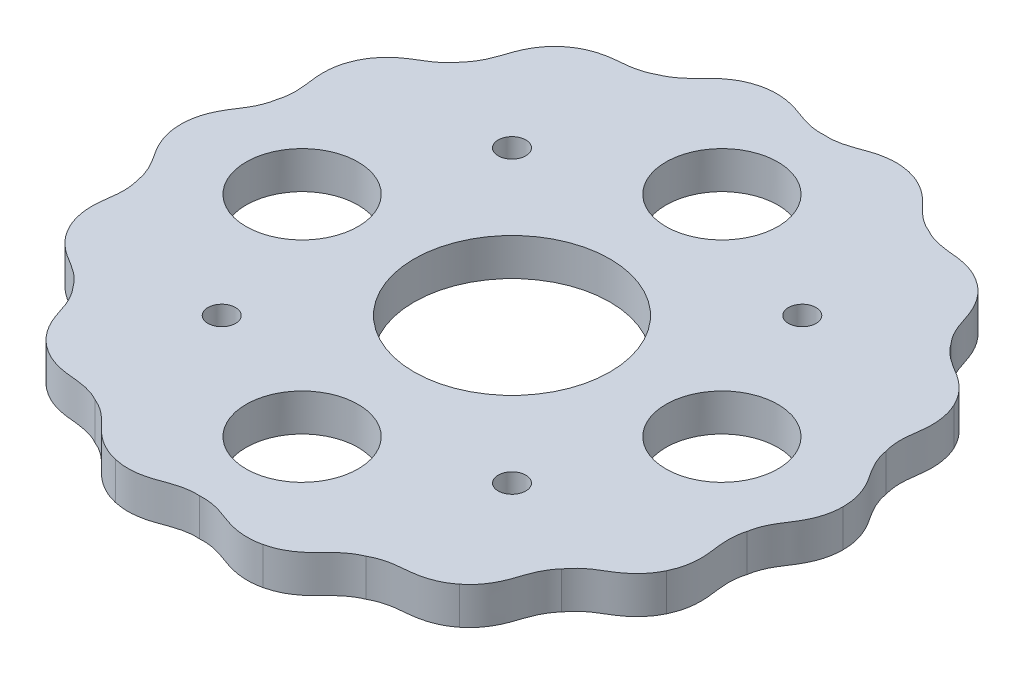
SolidWorks part; units mm, degrees
ref_plane "Front Plane" through (0, 0, 0) normal (0, 0, 1) x (1, 0, 0)
ref_plane "Top Plane" through (0, 0, 0) normal (0, 1, 0) x (1, 0, 0)
ref_plane "Right Plane" through (0, 0, 0) normal (1, 0, 0) x (0, 0, -1)
sketch "Sketch1" plane through (0, 0, 0) normal (0, 1, 0) x (1, 0, 0)
  line L0 (0, 0) -> (37.5, 0) construction
  line L1 (0, 0) -> (37.4807, 1.2019) construction
  line L2 (0, 0) -> (37.423, 2.4026) construction
  line L3 (0, 0) -> (37.3267, 3.6009) construction
  line L4 (0, 0) -> (37.1921, 4.7954) construction
  line L5 (0, 0) -> (37.0193, 5.985) construction
  line L6 (0, 0) -> (36.8085, 7.1684) construction
  line L7 (0, 0) -> (36.5598, 8.3445) construction
  line L8 (0, 0) -> (36.2736, 9.512) construction
  line L9 (0, 0) -> (35.95, 10.6698) construction
  line L10 (0, 0) -> (35.5896, 11.8166) construction
  line L11 (0, 0) -> (35.1926, 12.9512) construction
  line L12 (0, 0) -> (34.7594, 14.0725) construction
  line L13 (0, 0) -> (34.2905, 15.1794) construction
  line L14 (0, 0) -> (33.7863, 16.2706) construction
  line L15 (37.5, 0) -> (38.5, 0) construction
  line L16 (37.4807, 1.2019) -> (38.3521, 1.6927) construction
  line L17 (37.423, 2.4026) -> (37.9413, 3.2578) construction
  line L18 (37.3267, 3.6009) -> (37.3588, 4.6003) construction
  line L19 (37.1921, 4.7954) -> (36.7296, 5.682) construction
  line L20 (37.0193, 5.985) -> (36.1812, 6.5305) construction
  line L21 (36.8085, 7.1684) -> (35.8105, 7.2325) construction
  line L22 (36.5598, 8.3445) -> (35.5849, 8.122) construction
  line L23 (37, 0.0019) -> (37, 0)
  line L24 (33.3367, 16.052) -> (33.3358, 16.0537)
  line L25 (37, -0.0019) -> (37, 0)
  line L26 (33.3367, -16.052) -> (33.3358, -16.0537)
  line L27 (33.335, -16.0554) -> (33.3358, -16.0537)
  line L28 (23.0706, -28.9266) -> (23.0691, -28.9278)
  line L29 (23.0677, -28.9289) -> (23.0691, -28.9278)
  line L30 (8.2351, -36.0719) -> (8.2333, -36.0723)
  line L31 (8.2315, -36.0727) -> (8.2333, -36.0723)
  line L32 (-8.2315, -36.0727) -> (-8.2333, -36.0723)
  line L33 (-8.2351, -36.0719) -> (-8.2333, -36.0723)
  line L34 (-23.0677, -28.9289) -> (-23.0691, -28.9278)
  line L35 (-23.0706, -28.9266) -> (-23.0691, -28.9278)
  line L36 (-33.335, -16.0554) -> (-33.3358, -16.0537)
  line L37 (-33.3367, -16.052) -> (-33.3358, -16.0537)
  line L38 (-37, -0.0019) -> (-37, 0)
  line L39 (-37, 0.0019) -> (-37, 0)
  line L40 (-33.3367, 16.052) -> (-33.3358, 16.0537)
  line L41 (-33.335, 16.0554) -> (-33.3358, 16.0537)
  line L42 (-23.0706, 28.9266) -> (-23.0691, 28.9278)
  line L43 (-23.0677, 28.9289) -> (-23.0691, 28.9278)
  line L44 (-8.2351, 36.0719) -> (-8.2333, 36.0723)
  line L45 (-8.2315, 36.0727) -> (-8.2333, 36.0723)
  line L46 (8.2315, 36.0727) -> (8.2333, 36.0723)
  line L47 (8.2351, 36.0719) -> (8.2333, 36.0723)
  line L48 (23.0677, 28.9289) -> (23.0691, 28.9278)
  line L49 (23.0706, 28.9266) -> (23.0691, 28.9278)
  line L50 (33.335, 16.0554) -> (33.3358, 16.0537)
  line L51 (35.5, 0.0037) -> (35.5, 0)
  line L52 (31.986, 15.3995) -> (31.9844, 15.4029)
  line L53 (35.5, -0.0037) -> (35.5, 0)
  line L54 (31.986, -15.3995) -> (31.9844, -15.4029)
  line L55 (31.9828, -15.4062) -> (31.9844, -15.4029)
  line L56 (22.1368, -27.7527) -> (22.1339, -27.755)
  line L57 (22.131, -27.7573) -> (22.1339, -27.755)
  line L58 (7.9031, -34.6091) -> (7.8995, -34.6099)
  line L59 (7.8959, -34.6108) -> (7.8995, -34.6099)
  line L60 (-7.8959, -34.6108) -> (-7.8995, -34.6099)
  line L61 (-7.9031, -34.6091) -> (-7.8995, -34.6099)
  line L62 (-22.131, -27.7573) -> (-22.1339, -27.755)
  line L63 (-22.1368, -27.7527) -> (-22.1339, -27.755)
  line L64 (-31.9828, -15.4062) -> (-31.9844, -15.4029)
  line L65 (-31.986, -15.3995) -> (-31.9844, -15.4029)
  line L66 (-35.5, -0.0037) -> (-35.5, 0)
  line L67 (-35.5, 0.0037) -> (-35.5, 0)
  line L68 (-31.986, 15.3995) -> (-31.9844, 15.4029)
  line L69 (-31.9828, 15.4062) -> (-31.9844, 15.4029)
  line L70 (-22.1368, 27.7527) -> (-22.1339, 27.755)
  line L71 (-22.131, 27.7573) -> (-22.1339, 27.755)
  line L72 (-7.9031, 34.6091) -> (-7.8995, 34.6099)
  line L73 (-7.8959, 34.6108) -> (-7.8995, 34.6099)
  line L74 (7.8959, 34.6108) -> (7.8995, 34.6099)
  line L75 (7.9031, 34.6091) -> (7.8995, 34.6099)
  line L76 (22.131, 27.7573) -> (22.1339, 27.755)
  line L77 (22.1368, 27.7527) -> (22.1339, 27.755)
  line L78 (31.9828, 15.4062) -> (31.9844, 15.4029)
  circle A0 centre (0, 0) radius 35 construction
  circle A1 centre (37.5, 0) radius 2.5 construction
  circle A2 centre (0, 0) radius 37.5 construction
  spline S0 degree 3 poles (35.5849, 8.122) (35.6266, 7.5364) (36.0345, 6.7125) (36.7836, 5.6218) (37.4152, 4.5501) (38.2239, 2.702) (38.5014, 1.1074) (38.5, 0) knots 0 0 0 0 0.195516 0.310928 0.453873 0.621058 1 1 1 1
  spline S1 degree 3 poles (35.5849, 8.122) (35.3683, 8.6678) (35.3784, 9.5871) (35.5801, 10.8948) (35.6841, 12.1344) (35.611, 14.1503) (35.169, 15.7074) (34.6873, 16.7045) knots 0 0 0 0 0.195516 0.310928 0.453873 0.621058 1 1 1 1
  spline S2 degree 1 poles (34.1119, 7.7858) (33.3367, 16.052) knots 0 0 1 1 construction
  spline S3 degree 1 poles (34.1119, 7.7858) (37, 0.0019) knots 0 0 1 1 construction
  spline S4 degree 3 poles (33.3367, 16.052) (33.6005, 15.5058) (33.9037, 14.6401) (34.1146, 13.4372) (34.174, 12.5211) (34.1413, 11.5771) (34.0239, 10.6392) (33.8823, 9.6155) (33.9055, 8.625) (34.0243, 8.0514) (34.1119, 7.7858) knots 0.015853 0.015853 0.015853 0.015853 0.26189 0.384908 0.507927 0.630945 0.753963 0.876982 0.938491 1 1 1 1
  spline S5 degree 3 poles (34.1119, 7.7858) (34.1483, 7.5085) (34.2901, 6.9402) (34.6989, 6.0377) (35.2706, 5.1769) (35.7834, 4.3828) (36.2224, 3.5464) (36.5664, 2.6953) (36.8983, 1.52) (37.0008, 0.6085) (37, 0.0019) knots 0.015853 0.015853 0.015853 0.015853 0.077362 0.138872 0.26189 0.384908 0.507927 0.630945 0.753963 1 1 1 1
  spline S6 degree 3 poles (37, -0.0019) (37.0008, -0.6085) (36.8983, -1.52) (36.5664, -2.6953) (36.2224, -3.5464) (35.7834, -4.3828) (35.2706, -5.1769) (34.6989, -6.0377) (34.2901, -6.9402) (34.1483, -7.5085) (34.1119, -7.7858) knots 0.015853 0.015853 0.015853 0.015853 0.26189 0.384908 0.507927 0.630945 0.753963 0.876982 0.938491 1 1 1 1
  spline S7 degree 3 poles (34.1119, -7.7858) (34.0243, -8.0514) (33.9055, -8.625) (33.8823, -9.6155) (34.0239, -10.6392) (34.1413, -11.5771) (34.174, -12.5211) (34.1146, -13.4372) (33.9037, -14.6401) (33.6005, -15.5058) (33.3367, -16.052) knots 0.015853 0.015853 0.015853 0.015853 0.077362 0.138872 0.26189 0.384908 0.507927 0.630945 0.753963 1 1 1 1
  spline S8 degree 3 poles (33.335, -16.0554) (33.0725, -16.6022) (32.5847, -17.3791) (31.7758, -18.2939) (31.0965, -18.9115) (30.3381, -19.4746) (29.5316, -19.9675) (28.6429, -20.4951) (27.8831, -21.1308) (27.5087, -21.5813) (27.3556, -21.8154) knots 0.015853 0.015853 0.015853 0.015853 0.26189 0.384908 0.507927 0.630945 0.753963 0.876982 0.938491 1 1 1 1
  spline S9 degree 3 poles (27.3556, -21.8154) (27.1615, -22.0167) (26.8056, -22.4819) (26.3549, -23.3642) (26.0383, -24.348) (25.7371, -25.2439) (25.357, -26.1087) (24.906, -26.9083) (24.1941, -27.9005) (23.5453, -28.549) (23.0706, -28.9266) knots 0.015853 0.015853 0.015853 0.015853 0.077362 0.138872 0.26189 0.384908 0.507927 0.630945 0.753963 1 1 1 1
  spline S10 degree 3 poles (23.0677, -28.9289) (22.5939, -29.3077) (21.8173, -29.796) (20.6915, -30.2693) (19.8116, -30.531) (18.884, -30.7092) (17.9435, -30.8034) (16.9139, -30.8931) (15.9535, -31.1362) (15.4207, -31.3797) (15.1812, -31.5241) knots 0.015853 0.015853 0.015853 0.015853 0.26189 0.384908 0.507927 0.630945 0.753963 0.876982 0.938491 1 1 1 1
  spline S11 degree 3 poles (15.1812, -31.5241) (14.919, -31.6213) (14.3964, -31.886) (13.6076, -32.4854) (12.8955, -33.2344) (12.2354, -33.9109) (11.5177, -34.5251) (10.7645, -35.0499) (9.6926, -35.6349) (8.8266, -35.9377) (8.2351, -36.0719) knots 0.015853 0.015853 0.015853 0.015853 0.077362 0.138872 0.26189 0.384908 0.507927 0.630945 0.753963 1 1 1 1
  spline S12 degree 3 poles (8.2315, -36.0727) (7.6402, -36.2085) (6.7287, -36.3114) (5.5091, -36.2494) (4.6028, -36.1034) (3.6897, -35.8614) (2.8014, -35.5383) (1.8349, -35.1724) (0.8641, -34.9747) (0.2785, -34.9629) (0, -34.9891) knots 0.015853 0.015853 0.015853 0.015853 0.26189 0.384908 0.507927 0.630945 0.753963 0.876982 0.938491 1 1 1 1
  spline S13 degree 3 poles (0, -34.9891) (-0.2785, -34.9629) (-0.8641, -34.9747) (-1.8349, -35.1724) (-2.8014, -35.5383) (-3.6897, -35.8614) (-4.6028, -36.1034) (-5.5091, -36.2494) (-6.7287, -36.3114) (-7.6402, -36.2085) (-8.2315, -36.0727) knots 0.015853 0.015853 0.015853 0.015853 0.077362 0.138872 0.26189 0.384908 0.507927 0.630945 0.753963 1 1 1 1
  spline S14 degree 3 poles (-8.2351, -36.0719) (-8.8266, -35.9377) (-9.6926, -35.6349) (-10.7645, -35.0499) (-11.5177, -34.5251) (-12.2354, -33.9109) (-12.8955, -33.2344) (-13.6076, -32.4854) (-14.3964, -31.886) (-14.919, -31.6213) (-15.1812, -31.5241) knots 0.015853 0.015853 0.015853 0.015853 0.26189 0.384908 0.507927 0.630945 0.753963 0.876982 0.938491 1 1 1 1
  spline S15 degree 3 poles (-15.1812, -31.5241) (-15.4207, -31.3797) (-15.9535, -31.1362) (-16.9139, -30.8931) (-17.9435, -30.8034) (-18.884, -30.7092) (-19.8116, -30.531) (-20.6915, -30.2693) (-21.8173, -29.796) (-22.5939, -29.3077) (-23.0677, -28.9289) knots 0.015853 0.015853 0.015853 0.015853 0.077362 0.138872 0.26189 0.384908 0.507927 0.630945 0.753963 1 1 1 1
  spline S16 degree 3 poles (-23.0706, -28.9266) (-23.5453, -28.549) (-24.1941, -27.9005) (-24.906, -26.9083) (-25.357, -26.1087) (-25.7371, -25.2439) (-26.0383, -24.348) (-26.3549, -23.3642) (-26.8056, -22.4819) (-27.1615, -22.0167) (-27.3556, -21.8154) knots 0.015853 0.015853 0.015853 0.015853 0.26189 0.384908 0.507927 0.630945 0.753963 0.876982 0.938491 1 1 1 1
  spline S17 degree 3 poles (-27.3556, -21.8154) (-27.5087, -21.5813) (-27.8831, -21.1308) (-28.6429, -20.4951) (-29.5316, -19.9675) (-30.3381, -19.4746) (-31.0965, -18.9115) (-31.7758, -18.2939) (-32.5847, -17.3791) (-33.0725, -16.6022) (-33.335, -16.0554) knots 0.015853 0.015853 0.015853 0.015853 0.077362 0.138872 0.26189 0.384908 0.507927 0.630945 0.753963 1 1 1 1
  spline S18 degree 3 poles (-33.3367, -16.052) (-33.6005, -15.5058) (-33.9037, -14.6401) (-34.1146, -13.4372) (-34.174, -12.5211) (-34.1413, -11.5771) (-34.0239, -10.6392) (-33.8823, -9.6155) (-33.9055, -8.625) (-34.0243, -8.0514) (-34.1119, -7.7858) knots 0.015853 0.015853 0.015853 0.015853 0.26189 0.384908 0.507927 0.630945 0.753963 0.876982 0.938491 1 1 1 1
  spline S19 degree 3 poles (-34.1119, -7.7858) (-34.1483, -7.5085) (-34.2901, -6.9402) (-34.6989, -6.0377) (-35.2706, -5.1769) (-35.7834, -4.3828) (-36.2224, -3.5464) (-36.5664, -2.6953) (-36.8983, -1.52) (-37.0008, -0.6085) (-37, -0.0019) knots 0.015853 0.015853 0.015853 0.015853 0.077362 0.138872 0.26189 0.384908 0.507927 0.630945 0.753963 1 1 1 1
  spline S20 degree 3 poles (-37, 0.0019) (-37.0008, 0.6085) (-36.8983, 1.52) (-36.5664, 2.6953) (-36.2224, 3.5464) (-35.7834, 4.3828) (-35.2706, 5.1769) (-34.6989, 6.0377) (-34.2901, 6.9402) (-34.1483, 7.5085) (-34.1119, 7.7858) knots 0.015853 0.015853 0.015853 0.015853 0.26189 0.384908 0.507927 0.630945 0.753963 0.876982 0.938491 1 1 1 1
  spline S21 degree 3 poles (-34.1119, 7.7858) (-34.0243, 8.0514) (-33.9055, 8.625) (-33.8823, 9.6155) (-34.0239, 10.6392) (-34.1413, 11.5771) (-34.174, 12.5211) (-34.1146, 13.4372) (-33.9037, 14.6401) (-33.6005, 15.5058) (-33.3367, 16.052) knots 0.015853 0.015853 0.015853 0.015853 0.077362 0.138872 0.26189 0.384908 0.507927 0.630945 0.753963 1 1 1 1
  spline S22 degree 3 poles (-33.335, 16.0554) (-33.0725, 16.6022) (-32.5847, 17.3791) (-31.7758, 18.2939) (-31.0965, 18.9115) (-30.3381, 19.4746) (-29.5316, 19.9675) (-28.6429, 20.4951) (-27.8831, 21.1308) (-27.5087, 21.5813) (-27.3556, 21.8154) knots 0.015853 0.015853 0.015853 0.015853 0.26189 0.384908 0.507927 0.630945 0.753963 0.876982 0.938491 1 1 1 1
  spline S23 degree 3 poles (-27.3556, 21.8154) (-27.1615, 22.0167) (-26.8056, 22.4819) (-26.3549, 23.3642) (-26.0383, 24.348) (-25.7371, 25.2439) (-25.357, 26.1087) (-24.906, 26.9083) (-24.1941, 27.9005) (-23.5453, 28.549) (-23.0706, 28.9266) knots 0.015853 0.015853 0.015853 0.015853 0.077362 0.138872 0.26189 0.384908 0.507927 0.630945 0.753963 1 1 1 1
  spline S24 degree 3 poles (-23.0677, 28.9289) (-22.5939, 29.3077) (-21.8173, 29.796) (-20.6915, 30.2693) (-19.8116, 30.531) (-18.884, 30.7092) (-17.9435, 30.8034) (-16.9139, 30.8931) (-15.9535, 31.1362) (-15.4207, 31.3797) (-15.1812, 31.5241) knots 0.015853 0.015853 0.015853 0.015853 0.26189 0.384908 0.507927 0.630945 0.753963 0.876982 0.938491 1 1 1 1
  spline S25 degree 3 poles (-15.1812, 31.5241) (-14.919, 31.6213) (-14.3964, 31.886) (-13.6076, 32.4854) (-12.8955, 33.2344) (-12.2354, 33.9109) (-11.5177, 34.5251) (-10.7645, 35.0499) (-9.6926, 35.6349) (-8.8266, 35.9377) (-8.2351, 36.0719) knots 0.015853 0.015853 0.015853 0.015853 0.077362 0.138872 0.26189 0.384908 0.507927 0.630945 0.753963 1 1 1 1
  spline S26 degree 3 poles (-8.2315, 36.0727) (-7.6402, 36.2085) (-6.7287, 36.3114) (-5.5091, 36.2494) (-4.6028, 36.1034) (-3.6897, 35.8614) (-2.8014, 35.5383) (-1.8349, 35.1724) (-0.8641, 34.9747) (-0.2785, 34.9629) (0, 34.9891) knots 0.015853 0.015853 0.015853 0.015853 0.26189 0.384908 0.507927 0.630945 0.753963 0.876982 0.938491 1 1 1 1
  spline S27 degree 3 poles (0, 34.9891) (0.2785, 34.9629) (0.8641, 34.9747) (1.8349, 35.1724) (2.8014, 35.5383) (3.6897, 35.8614) (4.6028, 36.1034) (5.5091, 36.2494) (6.7287, 36.3114) (7.6402, 36.2085) (8.2315, 36.0727) knots 0.015853 0.015853 0.015853 0.015853 0.077362 0.138872 0.26189 0.384908 0.507927 0.630945 0.753963 1 1 1 1
  spline S28 degree 3 poles (8.2351, 36.0719) (8.8266, 35.9377) (9.6926, 35.6349) (10.7645, 35.0499) (11.5177, 34.5251) (12.2354, 33.9109) (12.8955, 33.2344) (13.6076, 32.4854) (14.3964, 31.886) (14.919, 31.6213) (15.1812, 31.5241) knots 0.015853 0.015853 0.015853 0.015853 0.26189 0.384908 0.507927 0.630945 0.753963 0.876982 0.938491 1 1 1 1
  spline S29 degree 3 poles (15.1812, 31.5241) (15.4207, 31.3797) (15.9535, 31.1362) (16.9139, 30.8931) (17.9435, 30.8034) (18.884, 30.7092) (19.8116, 30.531) (20.6915, 30.2693) (21.8173, 29.796) (22.5939, 29.3077) (23.0677, 28.9289) knots 0.015853 0.015853 0.015853 0.015853 0.077362 0.138872 0.26189 0.384908 0.507927 0.630945 0.753963 1 1 1 1
  spline S30 degree 3 poles (23.0706, 28.9266) (23.5453, 28.549) (24.1941, 27.9005) (24.906, 26.9083) (25.357, 26.1087) (25.7371, 25.2439) (26.0383, 24.348) (26.3549, 23.3642) (26.8056, 22.4819) (27.1615, 22.0167) (27.3556, 21.8154) knots 0.015853 0.015853 0.015853 0.015853 0.26189 0.384908 0.507927 0.630945 0.753963 0.876982 0.938491 1 1 1 1
  spline S31 degree 3 poles (27.3556, 21.8154) (27.5087, 21.5813) (27.8831, 21.1308) (28.6429, 20.4951) (29.5316, 19.9675) (30.3381, 19.4746) (31.0965, 18.9115) (31.7758, 18.2939) (32.5847, 17.3791) (33.0725, 16.6022) (33.335, 16.0554) knots 0.015853 0.015853 0.015853 0.015853 0.077362 0.138872 0.26189 0.384908 0.507927 0.630945 0.753963 1 1 1 1
  spline S32 degree 1 poles (32.6448, 7.451) (35.5, 0.0037) knots 0 0 1 1 construction
  spline S33 degree 1 poles (32.6448, 7.451) (31.986, 15.3995) knots 0 0 1 1 construction
  spline S34 degree 3 poles (35.5, 0.0037) (35.5006, 0.4959) (35.4183, 1.2336) (35.1496, 2.1927) (34.8707, 2.8896) (34.4997, 3.6015) (34.1394, 4.1652) (33.6939, 4.8394) (33.3068, 5.4873) (32.9751, 6.1975) (32.758, 6.8733) (32.6748, 7.2607) (32.6448, 7.451) knots 0.023011 0.023011 0.023011 0.023011 0.267258 0.389382 0.511505 0.633629 0.755753 0.816814 0.877876 0.938938 0.969469 1 1 1 1
  spline S35 degree 3 poles (32.6448, 7.451) (32.5893, 7.6354) (32.4961, 8.0206) (32.3985, 8.7236) (32.3893, 9.5074) (32.4569, 10.2591) (32.5657, 11.0598) (32.6458, 11.724) (32.6712, 12.5264) (32.6201, 13.2752) (32.446, 14.256) (32.2001, 14.9563) (31.986, 15.3995) knots 0.023011 0.023011 0.023011 0.023011 0.053542 0.084072 0.145134 0.206196 0.267258 0.389382 0.511505 0.633629 0.755753 1 1 1 1
  spline S36 degree 3 poles (32.6448, -7.451) (32.6748, -7.2607) (32.758, -6.8733) (32.9751, -6.1975) (33.3068, -5.4873) (33.6939, -4.8394) (34.1394, -4.1652) (34.4997, -3.6015) (34.8707, -2.8896) (35.1496, -2.1927) (35.4183, -1.2336) (35.5006, -0.4959) (35.5, -0.0037) knots 0.023011 0.023011 0.023011 0.023011 0.053542 0.084072 0.145134 0.206196 0.267258 0.389382 0.511505 0.633629 0.755753 1 1 1 1
  spline S37 degree 3 poles (31.986, -15.3995) (32.2001, -14.9563) (32.446, -14.256) (32.6201, -13.2752) (32.6712, -12.5264) (32.6458, -11.724) (32.5657, -11.0598) (32.4569, -10.2591) (32.3893, -9.5074) (32.3985, -8.7236) (32.4961, -8.0206) (32.5893, -7.6354) (32.6448, -7.451) knots 0.023011 0.023011 0.023011 0.023011 0.267258 0.389382 0.511505 0.633629 0.755753 0.816814 0.877876 0.938938 0.969469 1 1 1 1
  spline S38 degree 3 poles (26.1791, -20.8771) (26.2887, -20.7187) (26.5317, -20.4057) (27.0205, -19.8911) (27.6275, -19.3952) (28.2574, -18.9793) (28.9513, -18.5652) (29.5206, -18.2137) (30.1637, -17.7333) (30.7173, -17.2264) (31.3755, -16.4789) (31.7698, -15.8499) (31.9828, -15.4062) knots 0.023011 0.023011 0.023011 0.023011 0.053542 0.084072 0.145134 0.206196 0.267258 0.389382 0.511505 0.633629 0.755753 1 1 1 1
  spline S39 degree 3 poles (22.1368, -27.7527) (22.522, -27.4463) (23.0474, -26.922) (23.6297, -26.1139) (24.0007, -25.4614) (24.326, -24.7275) (24.542, -24.0943) (24.7914, -23.3257) (25.0566, -22.619) (25.405, -21.9169) (25.798, -21.3258) (26.0491, -21.0192) (26.1791, -20.8771) knots 0.023011 0.023011 0.023011 0.023011 0.267258 0.389382 0.511505 0.633629 0.755753 0.816814 0.877876 0.938938 0.969469 1 1 1 1
  spline S40 degree 3 poles (14.5283, -30.1683) (14.6957, -30.0732) (15.0505, -29.8966) (15.7143, -29.645) (16.4763, -29.4616) (17.2242, -29.3602) (18.0291, -29.2882) (18.6945, -29.2185) (19.4823, -29.0647) (20.201, -28.8482) (21.1184, -28.4603) (21.7465, -28.0647) (22.131, -27.7573) knots 0.023011 0.023011 0.023011 0.023011 0.053542 0.084072 0.145134 0.206196 0.267258 0.389382 0.511505 0.633629 0.755753 1 1 1 1
  spline S41 degree 3 poles (7.9031, -34.6091) (8.3831, -34.5002) (9.084, -34.2557) (9.9593, -33.7804) (10.5766, -33.3534) (11.1881, -32.8334) (11.6575, -32.3566) (12.2156, -31.7723) (12.7612, -31.2507) (13.3797, -30.7693) (13.9903, -30.4072) (14.3495, -30.2399) (14.5283, -30.1683) knots 0.023011 0.023011 0.023011 0.023011 0.267258 0.389382 0.511505 0.633629 0.755753 0.816814 0.877876 0.938938 0.969469 1 1 1 1
  spline S42 degree 3 poles (0, -33.4843) (0.1922, -33.4712) (0.5884, -33.4661) (1.2956, -33.5274) (2.0617, -33.6928) (2.7796, -33.926) (3.536, -34.2103) (4.1657, -34.4362) (4.9423, -34.6394) (5.6838, -34.7562) (6.6786, -34.8048) (7.4161, -34.7209) (7.8959, -34.6108) knots 0.023011 0.023011 0.023011 0.023011 0.053542 0.084072 0.145134 0.206196 0.267258 0.389382 0.511505 0.633629 0.755753 1 1 1 1
  spline S43 degree 3 poles (-7.8959, -34.6108) (-7.4161, -34.7209) (-6.6786, -34.8048) (-5.6838, -34.7562) (-4.9423, -34.6394) (-4.1657, -34.4362) (-3.536, -34.2103) (-2.7796, -33.926) (-2.0617, -33.6928) (-1.2956, -33.5274) (-0.5884, -33.4661) (-0.1922, -33.4712) (0, -33.4843) knots 0.023011 0.023011 0.023011 0.023011 0.267258 0.389382 0.511505 0.633629 0.755753 0.816814 0.877876 0.938938 0.969469 1 1 1 1
  spline S44 degree 3 poles (-14.5283, -30.1683) (-14.3495, -30.2399) (-13.9903, -30.4072) (-13.3797, -30.7693) (-12.7612, -31.2507) (-12.2156, -31.7723) (-11.6575, -32.3566) (-11.1881, -32.8334) (-10.5766, -33.3534) (-9.9593, -33.7804) (-9.084, -34.2557) (-8.3831, -34.5002) (-7.9031, -34.6091) knots 0.023011 0.023011 0.023011 0.023011 0.053542 0.084072 0.145134 0.206196 0.267258 0.389382 0.511505 0.633629 0.755753 1 1 1 1
  spline S45 degree 3 poles (-22.131, -27.7573) (-21.7465, -28.0647) (-21.1184, -28.4603) (-20.201, -28.8482) (-19.4823, -29.0647) (-18.6945, -29.2185) (-18.0291, -29.2882) (-17.2242, -29.3602) (-16.4763, -29.4616) (-15.7143, -29.645) (-15.0505, -29.8966) (-14.6957, -30.0732) (-14.5283, -30.1683) knots 0.023011 0.023011 0.023011 0.023011 0.267258 0.389382 0.511505 0.633629 0.755753 0.816814 0.877876 0.938938 0.969469 1 1 1 1
  spline S46 degree 3 poles (-26.1791, -20.8771) (-26.0491, -21.0192) (-25.798, -21.3258) (-25.405, -21.9169) (-25.0566, -22.619) (-24.7914, -23.3257) (-24.542, -24.0943) (-24.326, -24.7275) (-24.0007, -25.4614) (-23.6297, -26.1139) (-23.0474, -26.922) (-22.522, -27.4463) (-22.1368, -27.7527) knots 0.023011 0.023011 0.023011 0.023011 0.053542 0.084072 0.145134 0.206196 0.267258 0.389382 0.511505 0.633629 0.755753 1 1 1 1
  spline S47 degree 3 poles (-31.9828, -15.4062) (-31.7698, -15.8499) (-31.3755, -16.4789) (-30.7173, -17.2264) (-30.1637, -17.7333) (-29.5206, -18.2137) (-28.9513, -18.5652) (-28.2574, -18.9793) (-27.6275, -19.3952) (-27.0205, -19.8911) (-26.5317, -20.4057) (-26.2887, -20.7187) (-26.1791, -20.8771) knots 0.023011 0.023011 0.023011 0.023011 0.267258 0.389382 0.511505 0.633629 0.755753 0.816814 0.877876 0.938938 0.969469 1 1 1 1
  spline S48 degree 3 poles (-32.6448, -7.451) (-32.5893, -7.6354) (-32.4961, -8.0206) (-32.3985, -8.7236) (-32.3893, -9.5074) (-32.4569, -10.2591) (-32.5657, -11.0598) (-32.6458, -11.724) (-32.6712, -12.5264) (-32.6201, -13.2752) (-32.446, -14.256) (-32.2001, -14.9563) (-31.986, -15.3995) knots 0.023011 0.023011 0.023011 0.023011 0.053542 0.084072 0.145134 0.206196 0.267258 0.389382 0.511505 0.633629 0.755753 1 1 1 1
  spline S49 degree 3 poles (-35.5, -0.0037) (-35.5006, -0.4959) (-35.4183, -1.2336) (-35.1496, -2.1927) (-34.8707, -2.8896) (-34.4997, -3.6015) (-34.1394, -4.1652) (-33.6939, -4.8394) (-33.3068, -5.4873) (-32.9751, -6.1975) (-32.758, -6.8733) (-32.6748, -7.2607) (-32.6448, -7.451) knots 0.023011 0.023011 0.023011 0.023011 0.267258 0.389382 0.511505 0.633629 0.755753 0.816814 0.877876 0.938938 0.969469 1 1 1 1
  spline S50 degree 3 poles (-32.6448, 7.451) (-32.6748, 7.2607) (-32.758, 6.8733) (-32.9751, 6.1975) (-33.3068, 5.4873) (-33.6939, 4.8394) (-34.1394, 4.1652) (-34.4997, 3.6015) (-34.8707, 2.8896) (-35.1496, 2.1927) (-35.4183, 1.2336) (-35.5006, 0.4959) (-35.5, 0.0037) knots 0.023011 0.023011 0.023011 0.023011 0.053542 0.084072 0.145134 0.206196 0.267258 0.389382 0.511505 0.633629 0.755753 1 1 1 1
  spline S51 degree 3 poles (-31.986, 15.3995) (-32.2001, 14.9563) (-32.446, 14.256) (-32.6201, 13.2752) (-32.6712, 12.5264) (-32.6458, 11.724) (-32.5657, 11.0598) (-32.4569, 10.2591) (-32.3893, 9.5074) (-32.3985, 8.7236) (-32.4961, 8.0206) (-32.5893, 7.6354) (-32.6448, 7.451) knots 0.023011 0.023011 0.023011 0.023011 0.267258 0.389382 0.511505 0.633629 0.755753 0.816814 0.877876 0.938938 0.969469 1 1 1 1
  spline S52 degree 3 poles (-26.1791, 20.8771) (-26.2887, 20.7187) (-26.5317, 20.4057) (-27.0205, 19.8911) (-27.6275, 19.3952) (-28.2574, 18.9793) (-28.9513, 18.5652) (-29.5206, 18.2137) (-30.1637, 17.7333) (-30.7173, 17.2264) (-31.3755, 16.4789) (-31.7698, 15.8499) (-31.9828, 15.4062) knots 0.023011 0.023011 0.023011 0.023011 0.053542 0.084072 0.145134 0.206196 0.267258 0.389382 0.511505 0.633629 0.755753 1 1 1 1
  spline S53 degree 3 poles (-22.1368, 27.7527) (-22.522, 27.4463) (-23.0474, 26.922) (-23.6297, 26.1139) (-24.0007, 25.4614) (-24.326, 24.7275) (-24.542, 24.0943) (-24.7914, 23.3257) (-25.0566, 22.619) (-25.405, 21.9169) (-25.798, 21.3258) (-26.0491, 21.0192) (-26.1791, 20.8771) knots 0.023011 0.023011 0.023011 0.023011 0.267258 0.389382 0.511505 0.633629 0.755753 0.816814 0.877876 0.938938 0.969469 1 1 1 1
  spline S54 degree 3 poles (-14.5283, 30.1683) (-14.6957, 30.0732) (-15.0505, 29.8966) (-15.7143, 29.645) (-16.4763, 29.4616) (-17.2242, 29.3602) (-18.0291, 29.2882) (-18.6945, 29.2185) (-19.4823, 29.0647) (-20.201, 28.8482) (-21.1184, 28.4603) (-21.7465, 28.0647) (-22.131, 27.7573) knots 0.023011 0.023011 0.023011 0.023011 0.053542 0.084072 0.145134 0.206196 0.267258 0.389382 0.511505 0.633629 0.755753 1 1 1 1
  spline S55 degree 3 poles (-7.9031, 34.6091) (-8.3831, 34.5002) (-9.084, 34.2557) (-9.9593, 33.7804) (-10.5766, 33.3534) (-11.1881, 32.8334) (-11.6575, 32.3566) (-12.2156, 31.7723) (-12.7612, 31.2507) (-13.3797, 30.7693) (-13.9903, 30.4072) (-14.3495, 30.2399) (-14.5283, 30.1683) knots 0.023011 0.023011 0.023011 0.023011 0.267258 0.389382 0.511505 0.633629 0.755753 0.816814 0.877876 0.938938 0.969469 1 1 1 1
  spline S56 degree 3 poles (0, 33.4843) (-0.1922, 33.4712) (-0.5884, 33.4661) (-1.2956, 33.5274) (-2.0617, 33.6928) (-2.7796, 33.926) (-3.536, 34.2103) (-4.1657, 34.4362) (-4.9423, 34.6394) (-5.6838, 34.7562) (-6.6786, 34.8048) (-7.4161, 34.7209) (-7.8959, 34.6108) knots 0.023011 0.023011 0.023011 0.023011 0.053542 0.084072 0.145134 0.206196 0.267258 0.389382 0.511505 0.633629 0.755753 1 1 1 1
  spline S57 degree 3 poles (7.8959, 34.6108) (7.4161, 34.7209) (6.6786, 34.8048) (5.6838, 34.7562) (4.9423, 34.6394) (4.1657, 34.4362) (3.536, 34.2103) (2.7796, 33.926) (2.0617, 33.6928) (1.2956, 33.5274) (0.5884, 33.4661) (0.1922, 33.4712) (0, 33.4843) knots 0.023011 0.023011 0.023011 0.023011 0.267258 0.389382 0.511505 0.633629 0.755753 0.816814 0.877876 0.938938 0.969469 1 1 1 1
  spline S58 degree 3 poles (14.5283, 30.1683) (14.3495, 30.2399) (13.9903, 30.4072) (13.3797, 30.7693) (12.7612, 31.2507) (12.2156, 31.7723) (11.6575, 32.3566) (11.1881, 32.8334) (10.5766, 33.3534) (9.9593, 33.7804) (9.084, 34.2557) (8.3831, 34.5002) (7.9031, 34.6091) knots 0.023011 0.023011 0.023011 0.023011 0.053542 0.084072 0.145134 0.206196 0.267258 0.389382 0.511505 0.633629 0.755753 1 1 1 1
  spline S59 degree 3 poles (22.131, 27.7573) (21.7465, 28.0647) (21.1184, 28.4603) (20.201, 28.8482) (19.4823, 29.0647) (18.6945, 29.2185) (18.0291, 29.2882) (17.2242, 29.3602) (16.4763, 29.4616) (15.7143, 29.645) (15.0505, 29.8966) (14.6957, 30.0732) (14.5283, 30.1683) knots 0.023011 0.023011 0.023011 0.023011 0.267258 0.389382 0.511505 0.633629 0.755753 0.816814 0.877876 0.938938 0.969469 1 1 1 1
  spline S60 degree 3 poles (26.1791, 20.8771) (26.0491, 21.0192) (25.798, 21.3258) (25.405, 21.9169) (25.0566, 22.619) (24.7914, 23.3257) (24.542, 24.0943) (24.326, 24.7275) (24.0007, 25.4614) (23.6297, 26.1139) (23.0474, 26.922) (22.522, 27.4463) (22.1368, 27.7527) knots 0.023011 0.023011 0.023011 0.023011 0.053542 0.084072 0.145134 0.206196 0.267258 0.389382 0.511505 0.633629 0.755753 1 1 1 1
  spline S61 degree 3 poles (31.9828, 15.4062) (31.7698, 15.8499) (31.3755, 16.4789) (30.7173, 17.2264) (30.1637, 17.7333) (29.5206, 18.2137) (28.9513, 18.5652) (28.2574, 18.9793) (27.6275, 19.3952) (27.0205, 19.8911) (26.5317, 20.4057) (26.2887, 20.7187) (26.1791, 20.8771) knots 0.023011 0.023011 0.023011 0.023011 0.267258 0.389382 0.511505 0.633629 0.755753 0.816814 0.877876 0.938938 0.969469 1 1 1 1
  point P25 (0, 0)
  point P117 (0, 0)
  point P174 (0, 0)
  dimension "D1" = 70
  dimension "D2" = 5
  dimension "D4" = 25.714
  dimension "D5" = 1
  dimension "D7" = 180
  dimension "D8" = 207.551
  dimension "D6" = 1
  dimension "D9" = 1
  dimension "D10" = 235.102
  dimension "D11" = 1
  dimension "D12" = 1
  dimension "D13" = 1
  dimension "D14" = 1
  dimension "D15" = 1
  dimension "D16" = 262.653
  dimension "D17" = 290.204
  dimension "D18" = 317.755
  dimension "D19" = 345.306
  dimension "D20" = 1.5
  dimension "D22" = 3
  dimension "D3" = 15
  dimension "D21" = 14
  dimension "D23" = 14
extrude "Boss-Extrude3" add sketch "Sketch1" along normal blind 4 contours L51 L53 S36 S37 L54 L55 S38 S39 L56 L57 S40 S41 L58 L59 S42 S43 L60 L61 S44 S45 L62 L63 S46 S47 L64 L65 S48 S49 L66 L67 S50 S51 L68 L69 S52 S53 L70 L71 S54 S55 L72 L73 S56 S57 L74 L75 S58 S59 L76 L77 S60 S61 L78 L52 S35 S34
sketch "Sketch2" plane through (0, 4, 0) normal (0, 1, 0) x (1, 0, 0)
  line L0 (0, 0) -> (22.5, 0) construction
  line L1 (0, 0) -> (15.5563, 15.5563) construction
  circle A0 centre (0, 0) radius 10.5
  circle A1 centre (22.5, 0) radius 6
  circle A6 centre (15.5563, 15.5563) radius 1.48
  circle A7 centre (0, -22.5) radius 6
  circle A8 centre (15.5563, -15.5563) radius 1.48
  circle A9 centre (-22.5, 0) radius 6
  circle A10 centre (-15.5563, -15.5563) radius 1.48
  circle A11 centre (0, 22.5) radius 6
  circle A12 centre (-15.5563, 15.5563) radius 1.48
  point P6 (4.9, 24.7403)
  point P7 (0, 0)
  point P16 (0, 0)
  point P21 (0, 0)
  point P24 (0, 0)
  dimension "D3" = 12
  dimension "D1" = 21
  dimension "D6" = 2.96
  dimension "D2" = 22.5
  dimension "D4" = 45
  dimension "D5" = 22
  dimension "D7" = 4
extrude "Cut-Extrude1" cut sketch "Sketch2" against normal blind 5 contours A7 | A0 | A0 | A0 | L0 A0 | A0 L0 | A1 | A9 | A11 region at (22.5, 4, -5.8303) region at (-10.203, 4, 0) region at (0, 4, 22.5) region at (-22.5, 4, 0) region at (0, 4, -22.5)
extrude "Cut-Extrude2" cut sketch "Sketch2<4>" against normal blind 2.22 contours A12 | A10 | A8 | A6 region at (15.5563, 4, -15.5563) region at (15.5563, 4, 15.5563) region at (-15.5563, 4, 15.5563) region at (-15.5563, 4, -15.5563)
sketch "Sketch2<4>" plane through (0, 4, 0) normal (0, 1, 0) x (1, 0, 0) same geometry as "Sketch2"
equation "\"eccentricity\"= 1mm"
equation "\"Pin Diameter\"= 3mm"
equation "\"D5@Sketch1\" = \"eccentricity\""
equation "\"D6@Sketch1\" = \"eccentricity\""
equation "\"D9@Sketch1\" = \"eccentricity\""
equation "\"D11@Sketch1\" = \"eccentricity\""
equation "\"D12@Sketch1\" = \"eccentricity\""
equation "\"D14@Sketch1\" = \"eccentricity\""
equation "\"D13@Sketch1\" = \"eccentricity\""
equation "\"D15@Sketch1\" = \"eccentricity\""
equation "\"Disc Bearing Diameter\"=21"
equation "\"bearing_21_OD\"= 21mm"
equation "\"bearing_21_ID\"=15mm"
equation "\"pin_cirlce_diameter\"= 75mm"
equation "\"pin_diam\"= 6mm"
equation "\"gear_thickness\"= 4mm"
equation "\"ball_bearing_diam\"= 2.96mm"
equation "\"bearing_21_outer_clearance\"= 0mm'change this"
equation "\"bearing_21_inner_clearance\"=0mm'change this"
equation "\"bearing_15_OD\"= 15mm"
equation "\"bearing_15_ID\"=10mm"
equation "\"bearing_15_outer_clearance\"= 0mm'change this"
equation "\"bearing_15_inner_clearance\"= 0mm'change this"
equation "\"thrust_bearing_thickness\"= 5mm'measure this irl and change"
equation "\"D1@Sketch2\"=\"bearing_21_OD\"+\"bearing_21_outer_clearance\""
equation "\"D6@Sketch2\"=\"ball_bearing_diam\""
equation "\"D1@Cut-Extrude2\"=\"ball_bearing_diam\"*0.75"
